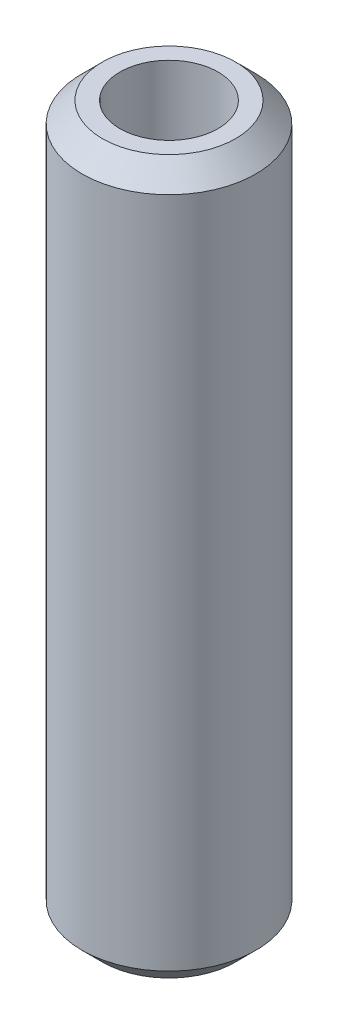
SolidWorks part; units mm, degrees
ref_plane "Front Plane" through (0, 0, 0) normal (0, 0, 1) x (1, 0, 0)
ref_plane "Top Plane" through (0, 0, 0) normal (0, 1, 0) x (1, 0, 0)
ref_plane "Right Plane" through (0, 0, 0) normal (1, 0, 0) x (0, 0, -1)
sketch "Sketch1" plane through (0, 0, 0) normal (0, 1, 0) x (1, 0, 0)
  circle A0 centre (0, 0) radius 25
  dimension "SHAFT_OD" = 50
extrude "Boss-Extrude1" add sketch "Sketch1" along normal blind 205.1799
sketch "Sketch2" plane through (0, 0, 0) normal (0, 1, 0) x (1, 0, 0)
  circle A0 centre (0, 0) radius 14.1292
  dimension "BORE_D" = 28.2584
extrude "Cut-Extrude1" cut sketch "Sketch2" along normal through all
chamfer "Chamfer1" distance 5.8553 angle 45 2 edges at (0, 205.1799, 25) (0, 0, 25)
